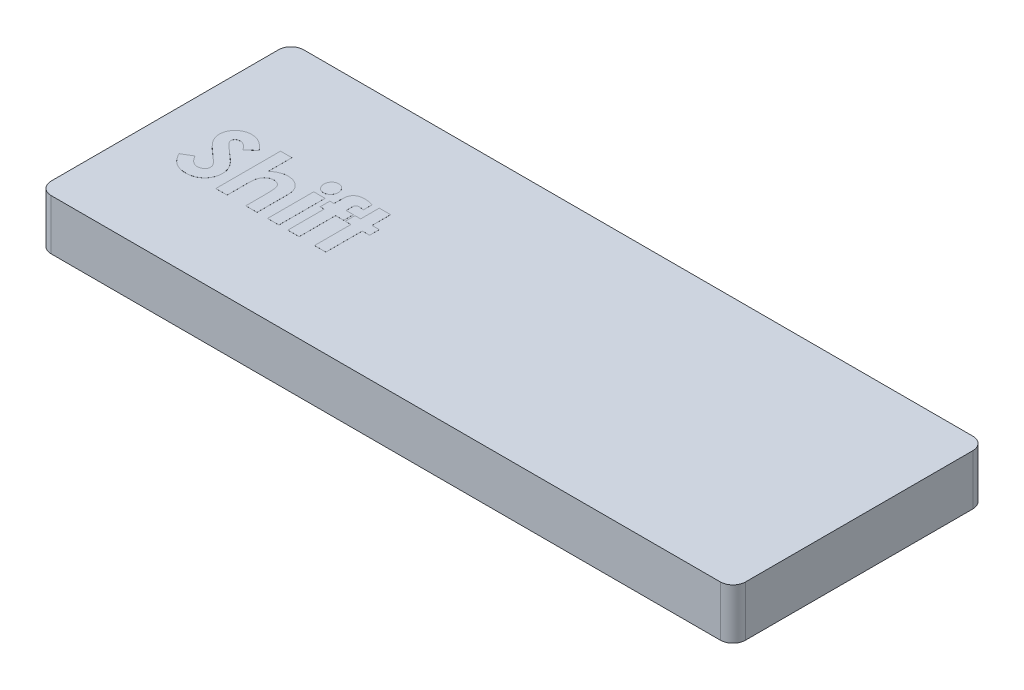
SolidWorks part; units mm, degrees
ref_plane "Front Plane" through (0, 0, 0) normal (0, 0, 1) x (1, 0, 0)
ref_plane "Top Plane" through (0, 0, 0) normal (0, 1, 0) x (1, 0, 0)
ref_plane "Right Plane" through (0, 0, 0) normal (1, 0, 0) x (0, 0, -1)
sketch "Sketch1" plane through (0, 0, 0) normal (0, 1, 0) x (1, 0, 0)
  line L0 (0, 0) -> (34.925, 0)
  line L1 (34.925, 0) -> (34.925, 12.7)
  line L2 (34.925, 12.7) -> (0, 12.7)
  line L3 (0, 12.7) -> (0, 0)
  dimension "D1" = 34.925
  dimension "D2" = 12.7
extrude "Boss-Extrude1" add sketch "Sketch1" along normal blind 2.54
fillet "Fillet1" radius 0.635 4 edges at (0, 1.27, -12.7) (34.925, 1.27, -12.7) (34.925, 1.27, 0) (0, 1.27, 0)
shell "Shell1" thickness 0.635 removed face at (17.4625, 0, -6.35)
sketch "Sketch2" plane through (0, 1.905, 0) normal (0, -1, 0) x (-1, 0, 0)
  line L0 (-0.635, 6.35) -> (-34.29, 6.35) construction
  line L1 (-0.635, 12.065) -> (-0.635, 0.635) construction
  line L2 (-34.29, 0.635) -> (-34.29, 12.065) construction
  line L3 (-17.4625, 0.635) -> (-17.4625, 12.065) construction
  line L4 (-0.635, 0.635) -> (-34.29, 0.635) construction
  line L5 (-34.29, 12.065) -> (-0.635, 12.065) construction
  circle A0 centre (-17.4625, 6.35) radius 2.54
  dimension "D1" = 5.08
extrude "Boss-Extrude2" add sketch "Sketch2" along normal up to surface (1.905 mm away) up to face at (17.4625, 0, -6.35)
sketch "Sketch3" plane through (0, 2.54, 0) normal (0, 1, 0) x (1, 0, 0)
  line L0 (34.925, 0.635) -> (34.925, 12.065) construction
  line L1 (0.635, 0) -> (34.29, 0) construction
  text T0 "<b>Shift</b>"
  dimension "D1" = 33.02
  dimension "D2" = 4.445
extrude "Boss-Extrude3" add sketch "Sketch3" along normal blind 0.0025
